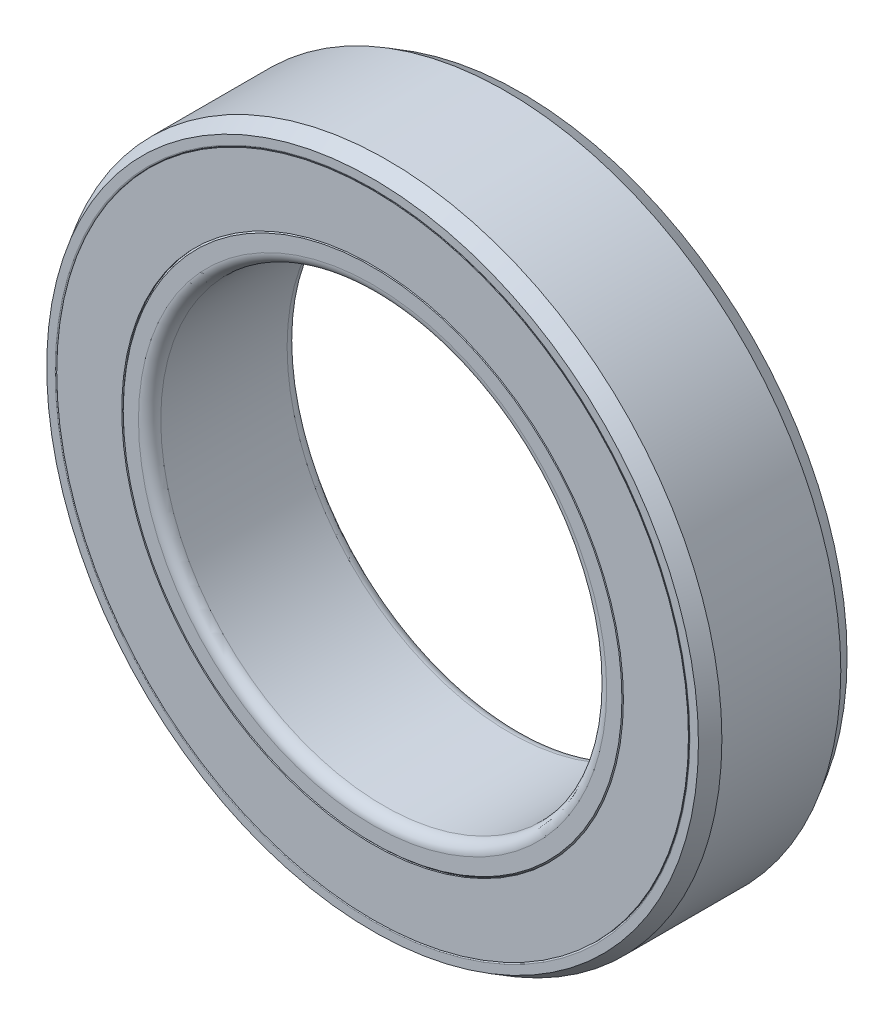
SolidWorks part; units mm, degrees
material "Alloy Steel"
ref_plane "Front Plane" through (0, 0, 0) normal (0, 0, 1) x (1, 0, 0)
ref_plane "Top Plane" through (0, 0, 0) normal (0, 1, 0) x (1, 0, 0)
ref_plane "Right Plane" through (0, 0, 0) normal (1, 0, 0) x (0, 0, -1)
sketch "Sketch1" plane through (0, 0, 0) normal (0, 0, 1) x (1, 0, 0)
  line L0 (0, 7.5) -> (0, 9) construction
  line L1 (0, 6) -> (0, 7.5) construction
  line L2 (0, 9) -> (0, 8.5) construction
  line L3 (0, 8.5) -> (0, 8) construction
  line L4 (0, 8) -> (0, 7.5) construction
  circle A0 centre (0, 0) radius 6
  circle A1 centre (0, 0) radius 9
  circle A2 centre (0, 0) radius 8.5 construction
  circle A4 centre (0, 0) radius 6.75 construction
  point P6 (0, 6.75)
  dimension "OD" = 18
  dimension "ID" = 12
sketch "Sketch2" plane through (0, 0, 0) normal (1, 0, 0) x (0, 0, -1)
  line L0 (-2, 9) -> (2, 9) construction
  line L1 (2, 9) -> (2, -9) construction
  line L2 (2, 0) -> (-2, 0) construction
  line L3 (-2, 6) -> (-2, -6) construction
  point P2 (0, 9)
  dimension "Width" = 4
  dimension "For Shaft Diameter" = 12
  dimension "For Housing ID" = 18
sketch "Sketch3" plane through (0, 0, 0) normal (1, 0, 0) x (0, 0, -1)
  line L0 (-1.6, -9) -> (1.6, -9)
  line L3 (-2, -8.54) -> (-2, -8.7691)
  line L4 (0, -6.75) -> (0, -8.5) construction
  line L5 (-1.6, -9) -> (-2, -8.7691)
  line L6 (-1.7, -6) -> (1.7, -6)
  line L7 (-0.8333, -8.5) -> (-0.8333, -8.6667) construction
  line L8 (-1.96, -6.75) -> (-0.8333, -6.75)
  line L9 (-2, -6.75) -> (0, -6.75) construction
  line L11 (-2, -8.5) -> (-2, -6.75) construction
  line L12 (-2, -6.71) -> (-2, -6.3)
  line L14 (-2, 0) -> (2, 0) construction
  line L15 (-1.96, -8.5) -> (-0.8333, -8.5)
  line L17 (0, 0) -> (0, -9) construction
  line L18 (-0.8333, -8.6667) -> (-0.8333, -8.8333) construction
  line L19 (1.6, -9) -> (2, -8.7691)
  line L20 (0, -8.5) -> (-2, -8.5) construction
  line L21 (-2, 6) -> (-2, -6) construction
  line L22 (-0.8333, -8.8333) -> (-0.8333, -9) construction
  line L30 (-2, -6.71) -> (-1.96, -6.75)
  line L31 (1.96, -6.75) -> (0.8333, -6.75)
  line L32 (2, -6.71) -> (1.96, -6.75)
  line L33 (2, -6.71) -> (2, -6.3)
  line L34 (1.96, -8.5) -> (0.8333, -8.5)
  line L35 (2, -8.54) -> (2, -8.7691)
  line L36 (0, 9) -> (0, -9) construction
  arc A0 (0, -6.4167) -> (0, -8.8333) centre (0, -7.625) ccw construction
  arc A1 (-0.8333, -6.75) -> (0.8333, -6.75) centre (0, -7.625) cw
  arc A2 (-0.8333, -8.5) -> (0.8333, -8.5) centre (0, -7.625) ccw
  arc A4 (-1.96, -8.5) -> (-2, -8.54) centre (-1.96, -8.54) ccw
  arc A5 (-1.7, -6) -> (-2, -6.3) centre (-1.7, -6.3) ccw
  arc A6 (1.7, -6) -> (2, -6.3) centre (1.7, -6.3) cw
  arc A7 (1.96, -8.5) -> (2, -8.54) centre (1.96, -8.54) cw
  point P28 (0, -7.625)
  point P46 (-2, -6)
  point P54 (0, -6)
  dimension "D4" = 0.04
  dimension "D7" = 0.3
  dimension "D5" = 45
  dimension "D6" = 0.04
  dimension "D3" = 0.4
  dimension "D2" = 60
revolve "Revolve1" add sketch "Sketch3" angle 360 about L14
sketch "Sketch4" plane through (0, 0, 0) normal (1, 0, 0) x (0, 0, -1)
  line L0 (-1.96, -8.5) -> (-0.8333, -8.5) construction
  line L1 (-2, -6.75) -> (-1.4063, -6.75)
  line L2 (-2, -6.75) -> (-2, -8.5)
  line L3 (-2, -8.5) -> (-1.4063, -8.5)
  line L4 (-1.4063, -6.75) -> (-1.4063, -8.5)
  line L5 (-2, -6.71) -> (-2, -6.3) construction
  line L6 (-2, -7.625) -> (-1.8021, -7.625) construction
  line L7 (-1.8021, -7.625) -> (-1.6042, -7.625) construction
  line L8 (-1.6042, -7.625) -> (-1.4063, -7.625) construction
  line L9 (-1.4063, -7.625) -> (-1.2083, -7.625) construction
  line L10 (-2, -8.5) -> (-2, -6.75) construction
  line L11 (-1.96, -6.75) -> (-0.8333, -6.75) construction
  arc A1 (0, -6.4167) -> (0, -8.8333) centre (0, -7.625) ccw construction
revolve "Revolve2" add sketch "Sketch4" angle 360 about L14
sketch "Sketch5" plane through (0, 0, 0) normal (1, 0, 0) x (0, 0, -1)
  line L2 (0, -6.4167) -> (0, -8.8333)
  arc A2 (0, -8.8333) -> (0, -6.4167) centre (0, -7.625) cw
revolve "Revolve3" add sketch "Sketch5" angle 360 about L17
pattern_circular "CirPattern1" count 7 over 360 about axis through (0, 0, 2) along (0, 0, -1) of bodies 138
equation "\"D4@Sketch3\"=\"Width@Sketch2\"*.01"
equation "\"D6@Sketch3\"=\"Width@Sketch2\"*.01"
equation "\"D7@Sketch3\"=\"Width@Sketch2\"*.075"
equation "\"D3@Sketch3\"=\"Width@Sketch2\"*.1"
